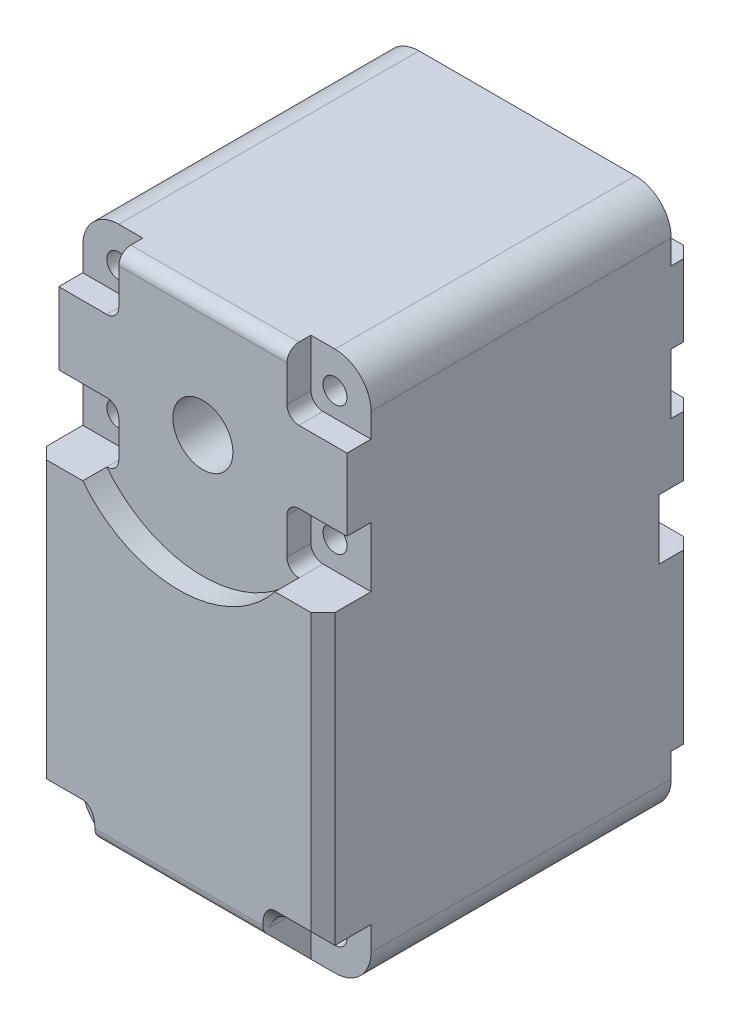
SolidWorks part; units mm, degrees
ref_plane "Plan de face" through (0, 0, 0) normal (0, 0, 1) x (1, 0, 0)
ref_plane "Plan de dessus" through (0, 0, 0) normal (0, 1, 0) x (1, 0, 0)
ref_plane "Plan de droite" through (0, 0, 0) normal (1, 0, 0) x (0, 0, -1)
sketch "Esquisse1" plane through (0, 0, 0) normal (0, 0, 1) x (1, 0, 0)
  line L0 (-64.239, 0) -> (105.761, 0) construction
  line L1 (-12, 22.5) -> (12, 22.5)
  line L2 (-12, 22.5) -> (-12, -22.5)
  line L3 (-12, -22.5) -> (12, -22.5)
  line L4 (12, 22.5) -> (12, -22.5)
  line L5 (0, -21.5957) -> (0, 93.0851) construction
  circle A0 centre (9, 19.5) radius 1
  circle A1 centre (9, 8.8) radius 1
  circle A2 centre (0, 12.8) radius 2.5
  circle A3 centre (-9, 19.5) radius 1
  circle A4 centre (-9, 8.8) radius 1
  circle A5 centre (9, -19.5) radius 1
  circle A6 centre (-9, -19.5) radius 1
  point P18 (0, 22.5)
  point P21 (12, 0)
  point P26 (-12, 0)
  dimension "D5" = 2
  dimension "D6" = 2
  dimension "D8" = 2.5
  dimension "D1" = 45
  dimension "D2" = 24
  dimension "D3" = 39
  dimension "D4" = 10.7
  dimension "D7" = 18
  dimension "D9" = 9.7
extrude "Boss.-Extru.1" add sketch "Esquisse1" against normal blind 31
sketch "Esquisse2" plane through (0, 0, 0) normal (0, 0, 1) x (1, 0, 0)
  line L0 (-19.8653, 0) -> (37.6602, 0) construction
  line L1 (0, 23.0829) -> (0, -25.4892) construction
  line L2 (-12, 22.5) -> (12, 22.5)
  line L3 (12, 22.5) -> (-12, 22.5) construction
  line L4 (12, 22.5) -> (12, 6.5)
  line L5 (12, -22.5) -> (12, 22.5) construction
  line L6 (12, 6.5) -> (8, 6.5)
  line L7 (-12, 6.5) -> (-8, 6.5)
  line L8 (-12, 22.5) -> (-12, 6.5)
  arc A0 (-8, 6.5) -> (8, 6.5) centre (0, 12.8) ccw
  point P19 (0, 22.5)
  dimension "D1" = 16
  dimension "D2" = 4
extrude "Enlèv. mat.-Extru.1" cut sketch "Esquisse2" against normal blind 2
fillet "Congé2" radius 3 4 edges at (12, 22.5, -16.5) (-12, 22.5, -16.5) (12, -22.5, -15.5) (-12, -22.5, -15.5)
sketch "Esquisse3" plane through (0, 0, 0) normal (0, 0, 1) x (1, 0, 0)
  line L0 (-21.0664, 0) -> (27.8873, 0) construction
  line L1 (0, 33.3468) -> (0, -28.5804) construction
  line L2 (12, 6.5) -> (12, 19.5) construction
  line L4 (12, 22.5) -> (7, 22.5)
  line L6 (12, 22.5) -> (12, 17.5)
  line L7 (12, 17.5) -> (7, 17.5)
  line L8 (7, 22.5) -> (7, 17.5)
  line L9 (9, 22.5) -> (-9, 22.5) construction
  line L10 (8, 6.5) -> (12, 6.5) construction
  line L11 (12, 11.5) -> (7, 11.5)
  line L12 (12, 11.5) -> (12, 6.5)
  line L13 (12, 6.5) -> (7, 6.5)
  line L14 (7, 11.5) -> (7, 6.5)
  line L15 (-12, 17.5) -> (-7, 17.5)
  line L16 (-12, 22.5) -> (-12, 17.5)
  line L17 (-12, 22.5) -> (-7, 22.5)
  line L18 (-7, 22.5) -> (-7, 17.5)
  line L19 (-12, 11.5) -> (-12, 6.5)
  line L20 (-12, 11.5) -> (-7, 11.5)
  line L21 (-7, 11.5) -> (-7, 6.5)
  line L22 (-12, 6.5) -> (-7, 6.5)
  line L23 (-12, -22.5) -> (-12, -17.5)
  line L24 (-12, -17.5) -> (-7, -17.5)
  line L25 (-7, -22.5) -> (-7, -17.5)
  line L26 (-12, -22.5) -> (-7, -22.5)
  line L27 (12, -22.5) -> (7, -22.5)
  line L28 (12, -22.5) -> (12, -17.5)
  line L29 (12, -17.5) -> (7, -17.5)
  line L30 (7, -22.5) -> (7, -17.5)
  dimension "D1" = 5
  dimension "D2" = 5
  dimension "D3" = 5
  dimension "D4" = 5
extrude "Enlèv. mat.-Extru.2" cut sketch "Esquisse3" against normal blind 4
sketch "Esquisse4" plane through (0, 0, -31) normal (0, 0, 1) x (1, 0, 0)
  line L0 (-21.0664, 0) -> (27.8873, 0) construction
  line L1 (0, 33.3468) -> (0, -28.5804) construction
  line L4 (12, 22.5) -> (7, 22.5)
  line L6 (12, 22.5) -> (12, 17.5)
  line L7 (12, 17.5) -> (7, 17.5)
  line L8 (7, 22.5) -> (7, 17.5)
  line L11 (12, 11.5) -> (7, 11.5)
  line L12 (12, 11.5) -> (12, 6.5)
  line L13 (12, 6.5) -> (7, 6.5)
  line L14 (7, 11.5) -> (7, 6.5)
  line L15 (-12, 17.5) -> (-7, 17.5)
  line L16 (-12, 22.5) -> (-12, 17.5)
  line L17 (-12, 22.5) -> (-7, 22.5)
  line L18 (-7, 22.5) -> (-7, 17.5)
  line L19 (-12, 11.5) -> (-12, 6.5)
  line L20 (-12, 11.5) -> (-7, 11.5)
  line L21 (-7, 11.5) -> (-7, 6.5)
  line L22 (-12, 6.5) -> (-7, 6.5)
  line L23 (-12, -22.5) -> (-12, -17.5)
  line L24 (-12, -17.5) -> (-7, -17.5)
  line L25 (-7, -22.5) -> (-7, -17.5)
  line L26 (-12, -22.5) -> (-7, -22.5)
  line L27 (12, -22.5) -> (7, -22.5)
  line L28 (12, -22.5) -> (12, -17.5)
  line L29 (12, -17.5) -> (7, -17.5)
  line L30 (7, -22.5) -> (7, -17.5)
  dimension "D1" = 5
  dimension "D2" = 5
  dimension "D3" = 5
  dimension "D4" = 5
extrude "Enlèv. mat.-Extru.3" cut sketch "Esquisse4" along normal blind 2
sketch "Esquisse5" plane through (0, 0, -31) normal (0, 0, -1) x (-1, 0, 0)
  line L0 (0, 22.5) -> (0, -22.5) construction
  line L1 (-7, 22.5) -> (7, 22.5) construction
  line L2 (7, -22.5) -> (-7, -22.5) construction
  line L3 (-2.5, -22.5) -> (2.5, -22.5)
  line L4 (2.5, -22.5) -> (2.5, -17.5)
  line L5 (2.5, -17.5) -> (1.75, -17.5)
  line L6 (1.75, -17.5) -> (1.75, -9.5)
  line L7 (1.75, -9.5) -> (3, -9.5)
  line L8 (3, -9.5) -> (4.5, -3.5)
  line L9 (4.5, -3.5) -> (12, -3.5)
  line L10 (12, 6.5) -> (12, -17.5) construction
  line L11 (12, -3.5) -> (12, 1.5)
  line L12 (12, 1.5) -> (-12, 1.5)
  line L13 (-2.5, -22.5) -> (-2.5, -17.5)
  line L14 (-2.5, -17.5) -> (-1.75, -17.5)
  line L15 (-1.75, -17.5) -> (-1.75, -9.5)
  line L16 (-1.75, -9.5) -> (-3, -9.5)
  line L17 (-3, -9.5) -> (-4.5, -3.5)
  line L18 (-4.5, -3.5) -> (-12, -3.5)
  line L19 (-12, -3.5) -> (-12, 1.5)
  point P25 (0, 1.5)
  dimension "D1" = 5
  dimension "D2" = 3.5
  dimension "D3" = 6
  dimension "D4" = 9
  dimension "D5" = 5
  dimension "D6" = 11
  dimension "D7" = 19
  dimension "D8" = 24
extrude "Enlèv. mat.-Extru.4" cut sketch "Esquisse5" against normal blind 2
chamfer "Chanfrein1" distance 4 angle 45 1 edges at (0, -22.5, 0)
chamfer "Chanfrein2" distance 1 angle 45 12 edges at (-12, 14.5, -31) (-12, 4, -31) (-12, -1, -29) (-12, -10.5, -31) (12, 14.5, -31) (12, -1, -29) (12, 4, -31) (12, -10.5, -31) (12, -5.5, 0) (9.5, -17.5, 0) (-9.5, -17.5, 0) (-12, -5.5, 0)
chamfer "Chanfrein3" distance 2 angle 45 3 edges at (0, 22.5, -31) (4.75, -22.5, -31) (-4.75, -22.5, -31)
fillet "Congé3" radius 1 30 edges at (1.75, -9.5, -30) (-1.75, -9.5, -30) (2.5, -17.5, -30) (2.5, -19, -31) (2.5, -21.5, -30) (4.5, -3.5, -30) (-4.5, -3.5, -30) (-2.5, -17.5, -30) (-2.5, -21.5, -30) (-2.5, -19, -31) (7, -17.5, -30) (-7, -17.5, -30) (-7, 6.5, -30) (-7, 11.5, -30) (-7, 17.5, -30) (0, -18.5, 0) (0, 22.5, -2) (7, 6.5, -30) (7, 11.5, -30) (7, 17.5, -30) (7, -17, -0.5) (7, -17.5, -2.5) (-7, -17.5, -2.5) (-7, -17, -0.5) (-7, 11.5, -3) (-7, 6.5, -3) (7, 6.5, -3) (7, 11.5, -3) (7, 17.5, -3) (-7, 17.5, -3)
sketch "Esquisse7" plane through (0, 0, 0) normal (0, 0, 1) x (1, 0, 0)
  line L0 (63.9607, 169.7657) -> (311.9607, 169.7657) construction
  line L1 (-11.4137, 83.2105) -> (236.5863, 83.2105) construction
  line L2 (56.9301, 155.3141) -> (304.9301, 155.3141) construction
  line L3 (50.4561, 157.6187) -> (298.4561, 157.6187) construction
  line L4 (50.7742, 157.4903) -> (298.7742, 157.4903) construction
